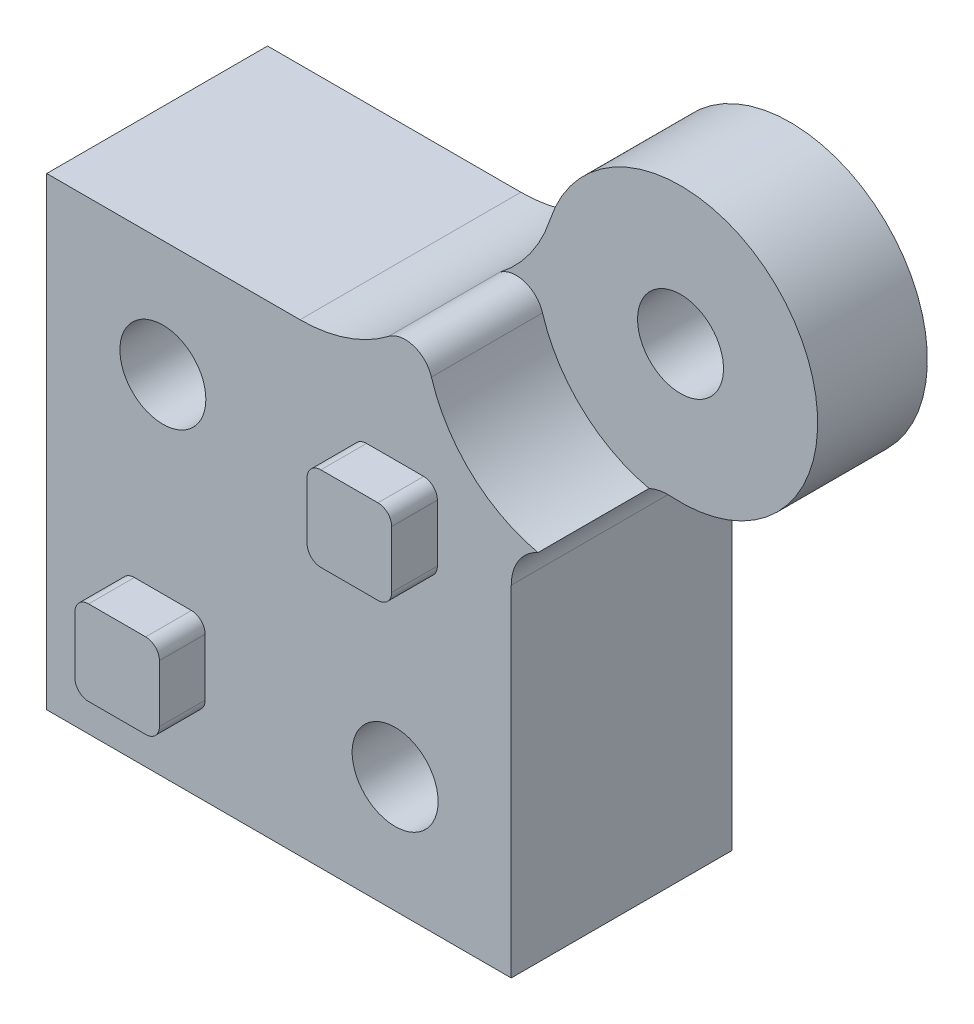
SolidWorks part; units mm, degrees
ref_plane "Front Plane" through (0, 0, 0) normal (0, 0, 1) x (1, 0, 0)
ref_plane "Top Plane" through (0, 0, 0) normal (0, 1, 0) x (1, 0, 0)
ref_plane "Right Plane" through (0, 0, 0) normal (1, 0, 0) x (0, 0, -1)
sketch "Sketch1" plane through (0, 0, 0) normal (0, 0, 1) x (1, 0, 0)
  line L0 (38.1, 165.1) -> (90.6036, 217.6036) construction
  line L1 (59.4614, 181.8386) -> (54.8386, 181.8386) construction
  line L2 (59.4614, 181.8386) -> (59.4614, 186.4614) construction
  line L3 (59.4614, 186.4614) -> (54.8386, 186.4614) construction
  line L4 (54.8386, 181.8386) -> (54.8386, 186.4614) construction
  line L5 (59.4614, 169.1386) -> (54.8386, 169.1386) construction
  line L6 (59.4614, 169.1386) -> (59.4614, 173.7614) construction
  line L7 (59.4614, 173.7614) -> (54.8386, 173.7614) construction
  line L8 (54.8386, 169.1386) -> (54.8386, 173.7614) construction
  line L9 (46.7614, 169.1386) -> (42.1386, 169.1386) construction
  line L10 (46.7614, 169.1386) -> (46.7614, 173.7614) construction
  line L11 (46.7614, 173.7614) -> (42.1386, 173.7614) construction
  line L12 (42.1386, 169.1386) -> (42.1386, 173.7614) construction
  line L13 (46.7614, 181.8386) -> (42.1386, 181.8386) construction
  line L14 (46.7614, 181.8386) -> (46.7614, 186.4614) construction
  line L15 (46.7614, 186.4614) -> (42.1386, 186.4614) construction
  line L16 (42.1386, 181.8386) -> (42.1386, 186.4614) construction
  line L17 (38.1, 165.1) -> (63.5, 165.1) construction
  line L18 (38.1, 165.1) -> (38.1, 190.5) construction
  line L19 (38.1, 190.5) -> (63.5, 190.5) construction
  line L20 (63.5, 165.1) -> (63.5, 190.5) construction
  line L21 (66.682, 205.8881) -> (66.682, 160.5985) construction
  line L22 (95.264, 165.1) -> (95.264, 190.5) construction
  line L23 (95.264, 165.1) -> (69.864, 165.1) construction
  line L24 (73.9026, 173.7614) -> (78.5254, 173.7614) construction
  line L25 (78.5254, 169.1386) -> (78.5254, 173.7614) construction
  line L26 (73.9026, 169.1386) -> (73.9026, 173.7614) construction
  line L27 (73.9026, 169.1386) -> (78.5254, 169.1386) construction
  line L28 (91.2254, 169.1386) -> (91.2254, 173.7614) construction
  line L29 (86.6026, 169.1386) -> (91.2254, 169.1386) construction
  line L30 (86.6026, 169.1386) -> (86.6026, 173.7614) construction
  line L31 (86.6026, 173.7614) -> (91.2254, 173.7614) construction
  line L32 (86.6026, 181.8386) -> (91.2254, 181.8386) construction
  line L33 (91.2254, 181.8386) -> (91.2254, 186.4614) construction
  line L34 (86.6026, 186.4614) -> (91.2254, 186.4614) construction
  line L35 (86.6026, 181.8386) -> (86.6026, 186.4614) construction
  line L36 (73.9026, 181.8386) -> (78.5254, 181.8386) construction
  line L37 (73.9026, 181.8386) -> (73.9026, 186.4614) construction
  line L38 (73.9026, 186.4614) -> (78.5254, 186.4614) construction
  line L39 (78.5254, 181.8386) -> (78.5254, 186.4614) construction
  line L40 (95.264, 190.5) -> (69.864, 190.5) construction
  line L41 (69.864, 165.1) -> (69.864, 190.5) construction
  circle A0 centre (66.682, 193.682) radius 2.35 construction
  circle A1 centre (66.682, 193.682) radius 7.5 construction
  dimension "D1" = 4.6228
  dimension "D6" = 4.7
  dimension "D7" = 4.5
  dimension "D10" = 15
  dimension "D2" = 4.0386
  dimension "D3" = 4.0386
  dimension "D4" = 45
  dimension "D5" = 25.4
  dimension "D8" = 8.0772
  dimension "D9" = 8.0772
sketch "Sketch2" plane through (0, 0, 0) normal (0, 0, 1) x (1, 0, 0)
  line L0 (59.4614, 186.4614) -> (54.8386, 186.4614)
  line L1 (54.8386, 186.4614) -> (54.8386, 181.8386)
  line L2 (54.8386, 181.8386) -> (59.4614, 181.8386)
  line L3 (59.4614, 181.8386) -> (59.4614, 186.4614)
  line L8 (42.1386, 173.7614) -> (42.1386, 169.1386)
  line L9 (42.1386, 169.1386) -> (46.7614, 169.1386)
  line L10 (46.7614, 169.1386) -> (46.7614, 173.7614)
  line L11 (46.7614, 173.7614) -> (42.1386, 173.7614)
  circle A0 centre (44.45, 184.15) radius 2.35
  circle A1 centre (57.15, 171.45) radius 2.35
extrude "Boss-Extrude1" add sketch "Sketch2" along normal blind 2.5
sketch "Sketch3" plane through (0, 0, 0) normal (0, 0, 1) x (1, 0, 0)
  line L0 (38.1, 190.5) -> (63.5, 190.5) construction
  line L1 (63.5, 165.1) -> (63.5, 190.5) construction
  line L2 (63.5, 186.4614) -> (63.5, 165.1)
  line L3 (63.5, 165.1) -> (38.1, 165.1)
  line L4 (38.1, 165.1) -> (38.1, 190.5)
  line L5 (38.1, 190.5) -> (59.4614, 190.5)
  arc A0 (59.4614, 190.5) -> (63.5, 186.4614) centre (66.682, 193.682) ccw
extrude "Boss-Extrude2" add sketch "Sketch3" against normal blind 6.075
sketch "Sketch4" plane through (0, 0, -6.075) normal (0, 0, -1) x (-1, 0, 0)
  line L0 (-38.1, 190.5) -> (-59.8904, 190.5)
  line L1 (-63.5, 165.1) -> (-63.5, 186.8904)
  line L2 (-63.5, 165.1) -> (-38.1, 165.1)
  line L3 (-38.1, 165.1) -> (-38.1, 190.5)
  circle A1 centre (-66.682, 193.682) radius 2.35
  circle A2 centre (-66.682, 193.682) radius 7.5
sketch "Sketch6" plane through (0, 0, 2.5) normal (0, 0, 1) x (1, 0, 0)
  circle A0 centre (44.45, 184.15) radius 2.35
  circle A1 centre (57.15, 171.45) radius 2.35
extrude "Cut-Extrude1" cut sketch "Sketch6" against normal through all
extrude "Boss-Extrude4" add sketch "Sketch4" along normal blind 6
fillet "Fillet2" radius 2.5 1 edges at (63.5, 186.8904, -9.075)
fillet "Fillet3" radius 8 1 edges at (59.8904, 190.5, -9.075)
sketch "Sketch7" plane through (0, 0, -6.075) normal (0, 0, 1) x (1, 0, 0)
  circle A0 centre (44.45, 184.15) radius 2.35
  circle A1 centre (57.15, 171.45) radius 2.35
extrude "Cut-Extrude2" cut sketch "Sketch7" against normal through all
fillet "Fillet4" radius 1.5 1 edges at (58.825, 194.4095, -3.0375)
fillet "Fillet5" radius 0.75 8 edges at (59.4614, 186.4614, 1.25) (59.4614, 181.8386, 1.25) (54.8386, 186.4614, 1.25) (54.8386, 181.8386, 1.25) (46.7614, 173.7614, 1.25) (46.7614, 169.1386, 1.25) (42.1386, 169.1386, 1.25) (42.1386, 173.7614, 1.25)
